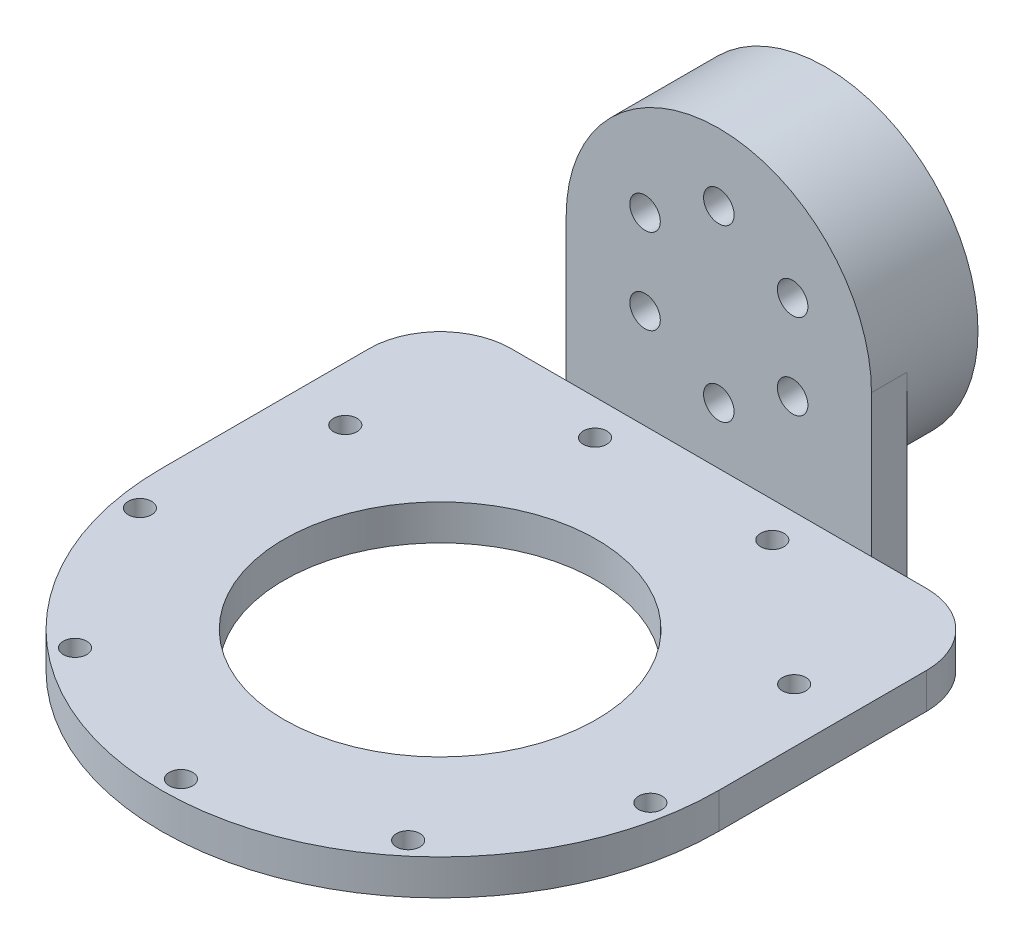
SolidWorks part; units mm, degrees
material "ABS"
ref_plane "正面" through (0, 0, 0) normal (0, 0, 1) x (1, 0, 0)
ref_plane "平面" through (0, 0, 0) normal (0, 1, 0) x (1, 0, 0)
ref_plane "右側面" through (0, 0, 0) normal (1, 0, 0) x (0, 0, -1)
sketch "ｽｹｯﾁ1" plane through (0, 0, 0) normal (0, 0, 1) x (1, 0, 0)
  circle A0 centre (0, 0) radius 21.5
  dimension "D1" = 43
extrude "ﾎﾞｽ - 押し出し1" add sketch "ｽｹｯﾁ1" along normal blind 10
sketch "ｽｹｯﾁ2" plane through (0, 0, 10) normal (0, 0, 1) x (1, 0, 0)
  line L0 (-21.5, 0) -> (-21.5, -25)
  line L1 (21.5, 0) -> (21.5, -25)
  line L2 (21.5, -25) -> (-21.5, -25)
  line L3 (21.5, 0) -> (-21.5, 0) construction
  arc A0 (21.5, 0) -> (-21.5, 0) centre (0, 0) ccw
  circle A1 centre (0, 0) radius 21.5 construction
  point P8 (0, 0)
  point P9 (-26.9297, -3.2173)
  dimension "D1" = 25
extrude "ﾎﾞｽ - 押し出し2" add sketch "ｽｹｯﾁ2" along normal blind 5
sketch "ｽｹｯﾁ3" plane through (0, -25, 0) normal (0, -1, 0) x (1, 0, 0)
  line L0 (-21.5, 15) -> (21.5, 15) construction
  line L1 (-39.25, 54.25) -> (-39.25, 15)
  line L2 (-39.25, 15) -> (39.25, 15)
  line L3 (39.25, 15) -> (39.25, 54.25)
  arc A0 (39.25, 54.25) -> (-39.25, 54.25) centre (0, 54.25) ccw
  point P1 (0, 15)
  dimension "D1" = 78.5
extrude "ﾎﾞｽ - 押し出し3" add sketch "ｽｹｯﾁ3" against normal blind 5
fillet "ﾌｨﾚｯﾄ1" radius 10 2 edges at (-39.25, -22.5, 15) (39.25, -22.5, 15)
sketch "ｽｹｯﾁ4" plane through (0, -20, 0) normal (0, 1, 0) x (1, 0, 0)
  line L0 (-39.25, -54.25) -> (39.25, -54.25) construction
  circle A0 centre (0, -54.25) radius 22
  dimension "D1" = 44
extrude "ｶｯﾄ - 押し出し1" cut sketch "ｽｹｯﾁ4" against normal through all
sketch "ｽｹｯﾁ5" plane through (0, -20, 0) normal (0, 1, 0) x (1, 0, 0)
  line L0 (0, -54.25) -> (0, -93.5) construction
  arc A0 (-39.25, -54.25) -> (39.25, -54.25) centre (0, -54.25) ccw construction
  circle A1 centre (0, -90.75) radius 1.65
  circle A2 centre (-23.4617, -82.2106) radius 1.65
  circle A3 centre (-35.9455, -60.5882) radius 1.65
  circle A4 centre (-31.6099, -36) radius 1.65
  circle A5 centre (-12.4837, -19.9512) radius 1.65
  circle A6 centre (12.4837, -19.9512) radius 1.65
  circle A7 centre (31.6099, -36) radius 1.65
  circle A8 centre (35.9455, -60.5882) radius 1.65
  circle A9 centre (23.4617, -82.2106) radius 1.65
  point P27 (0, -54.25)
  dimension "D1" = 3.3
  dimension "D2" = 36.5
  dimension "D3" = 9
extrude "ｶｯﾄ - 押し出し2" cut sketch "ｽｹｯﾁ5" against normal through all
sketch "ｽｹｯﾁ6" plane through (0, 0, 15) normal (0, 0, 1) x (1, 0, 0)
  line L0 (0, 0) -> (0, 12) construction
  circle A0 centre (0, 12) radius 2.15
  circle A1 centre (10.3923, 6) radius 2.15
  circle A2 centre (10.3923, -6) radius 2.15
  circle A3 centre (0, -12) radius 2.15
  circle A4 centre (-10.3923, -6) radius 2.15
  circle A5 centre (-10.3923, 6) radius 2.15
  point P4 (0, 0)
  point P17 (0, 0)
  dimension "D1" = 4.3
  dimension "D3" = 12
  dimension "D2" = 6
extrude "ｶｯﾄ - 押し出し3" cut sketch "ｽｹｯﾁ6" against normal through all
